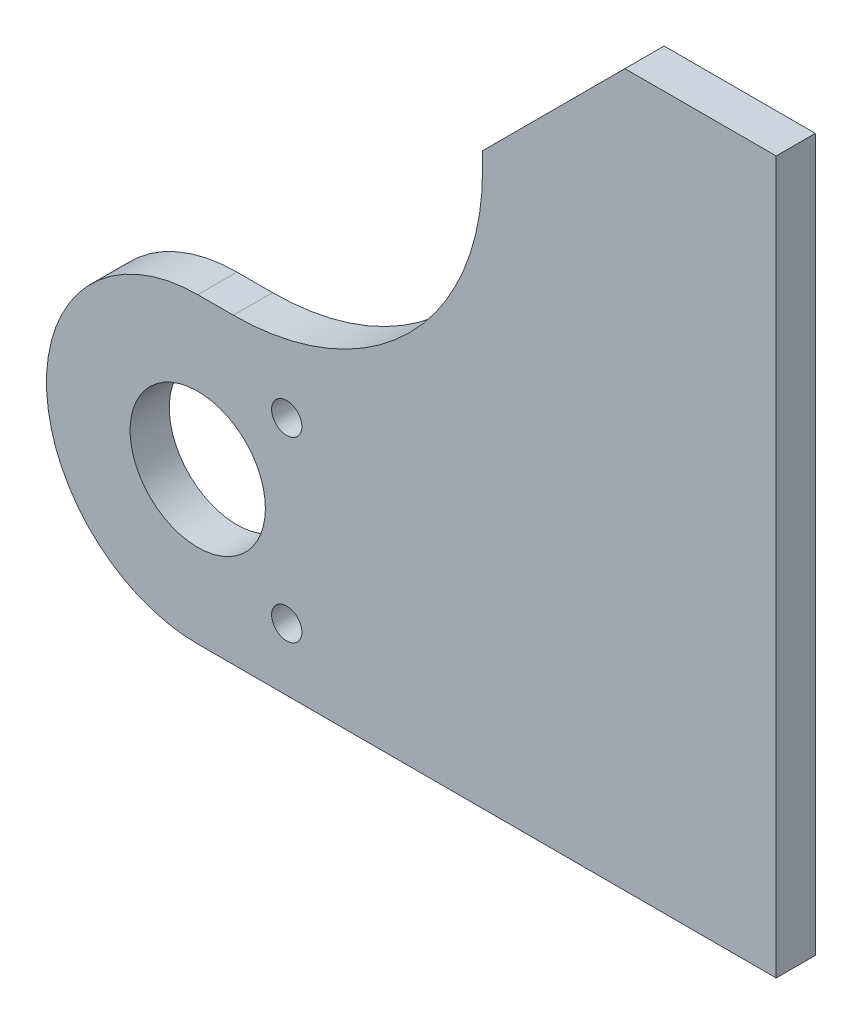
SolidWorks part; units mm, degrees
material "1.0037 (S235JR)"
ref_plane "E_Rechts" through (0, 0, 0) normal (0, 0, 1) x (1, 0, 0)
ref_plane "E_Oben" through (0, 0, 0) normal (0, 1, 0) x (1, 0, 0)
ref_plane "E_Vorne" through (0, 0, 0) normal (1, 0, 0) x (0, 0, -1)
sketch "Skizze1" plane through (0, 0, 0) normal (0, 0, 1) x (1, 0, 0)
  line L0 (0, 42.5) -> (10, 42.5)
  line L1 (80, 112.5) -> (80, 117.5)
  line L2 (120, 157.5) -> (162.5, 157.5)
  line L3 (162.5, 157.5) -> (162.5, -42.5)
  line L4 (162.5, -42.5) -> (0, -42.5)
  line L5 (0, -55) -> (0, 55) construction
  line L6 (80, 117.5) -> (120, 157.5)
  circle A0 centre (0, 0) radius 19
  arc A1 (0, 42.5) -> (0, -42.5) centre (0, 0) ccw
  arc A2 (80, 112.5) -> (10, 42.5) centre (10, 112.5) cw
  point P6 (80, 157.5)
  dimension "D1" = 38
  dimension "D2" = 85
  dimension "D3" = 162.5
  dimension "D4" = 70
  dimension "D5" = 10
  dimension "D6" = 82.5
  dimension "D7" = 200
  dimension "D8" = 162.5
extrude "Aufsatz-Linear austragen1" add sketch "Skizze1" along normal blind 4 and the other way blind 7
hole_wizard "M10 Gewindebohrung1" positions "Skizze2" profile "Skizze3" tap size "M10" standard "DIN" end condition through all
sketch "Skizze2" plane through (0, 0, 4) normal (0, 0, 1) x (1, 0, 0)
  line L0 (0, -55) -> (0, 55) construction
  line L1 (55, 0) -> (-55, 0) construction
  point P0 (25, -25)
  point P2 (25, 25)
  dimension "D1" = 25
  dimension "D2" = 0
  dimension "D3" = 50
  dimension "D4" = 25
cosmetic thread "Bohrungsgewinde1" parameters "D2"=10
cosmetic thread "Bohrungsgewinde2" parameters "D2"=10
sketch "Skizze3" plane through (25, -25, 4) normal (1, 0, 0) x (0, -1, 0)
  line L0 (0, 0) -> (0, 11)
  line L1 (0, 11) -> (4.25, 11)
  line L2 (4.25, 11) -> (4.25, 0)
  line L5 (4.25, 0) -> (0, 0)
  line L11 (0, -6.35) -> (0, 107.95) construction
  dimension "Bohrerdurchmesser" = 8.5
  dimension "Bohrungstiefe" = 11
